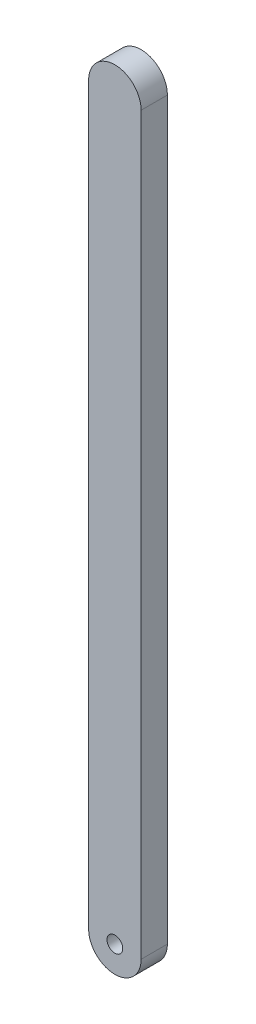
SolidWorks part; units mm, degrees
ref_plane "Plan de face" through (0, 0, 0) normal (0, 0, 1) x (1, 0, 0)
ref_plane "Plan de dessus" through (0, 0, 0) normal (0, 1, 0) x (1, 0, 0)
ref_plane "Plan de droite" through (0, 0, 0) normal (1, 0, 0) x (0, 0, -1)
sketch "Esquisse1" plane through (0, 0, 0) normal (0, 0, 1) x (1, 0, 0)
  line L1 (-5, 75) -> (5, 75)
  line L2 (-5, 75) -> (-5, -75)
  line L3 (-5, -75) -> (5, -75)
  line L4 (5, 75) -> (5, -75)
  line L5 (-5, 75) -> (5, -75) construction
  line L6 (-5, -75) -> (5, 75) construction
  point P0 (0, 0)
  dimension "D1" = 150
  dimension "D2" = 10
extrude "Boss.-Extru.1" add sketch "Esquisse1" along normal blind 5
fillet "Congé1" 2 edges at (-5, 75, 2.5) (5, 75, 2.5) type full round first side face at (-5, 0, 2.5) second side face at (5, 0, 2.5) middle face at (0, 75, 2.5)
fillet "Congé2" 2 edges at (-5, -75, 2.5) (5, -75, 2.5) type full round first side face at (-5, -2.5, 2.5) second side face at (5, -2.5, 2.5) middle face at (0, -75, 2.5)
sketch "Esquisse2" plane through (0, 0, 5) normal (0, 0, 1) x (1, 0, 0)
  circle A0 centre (0, 70) radius 2.5
  circle A1 centre (0, -70) radius 1.5
  dimension "D1" = 5
  dimension "D2" = 3
extrude "Enlèv. mat.-Extru.1" cut sketch "Esquisse2" against normal through all
sketch "Esquisse3" plane through (0, 0, 5) normal (0, 0, 1) x (1, 0, 0)
  circle A0 centre (0, 70) radius 2.5 construction
  circle A1 centre (0, 70) radius 2.5
extrude "Boss.-Extru.2" add sketch "Esquisse3" against normal blind 2.5
